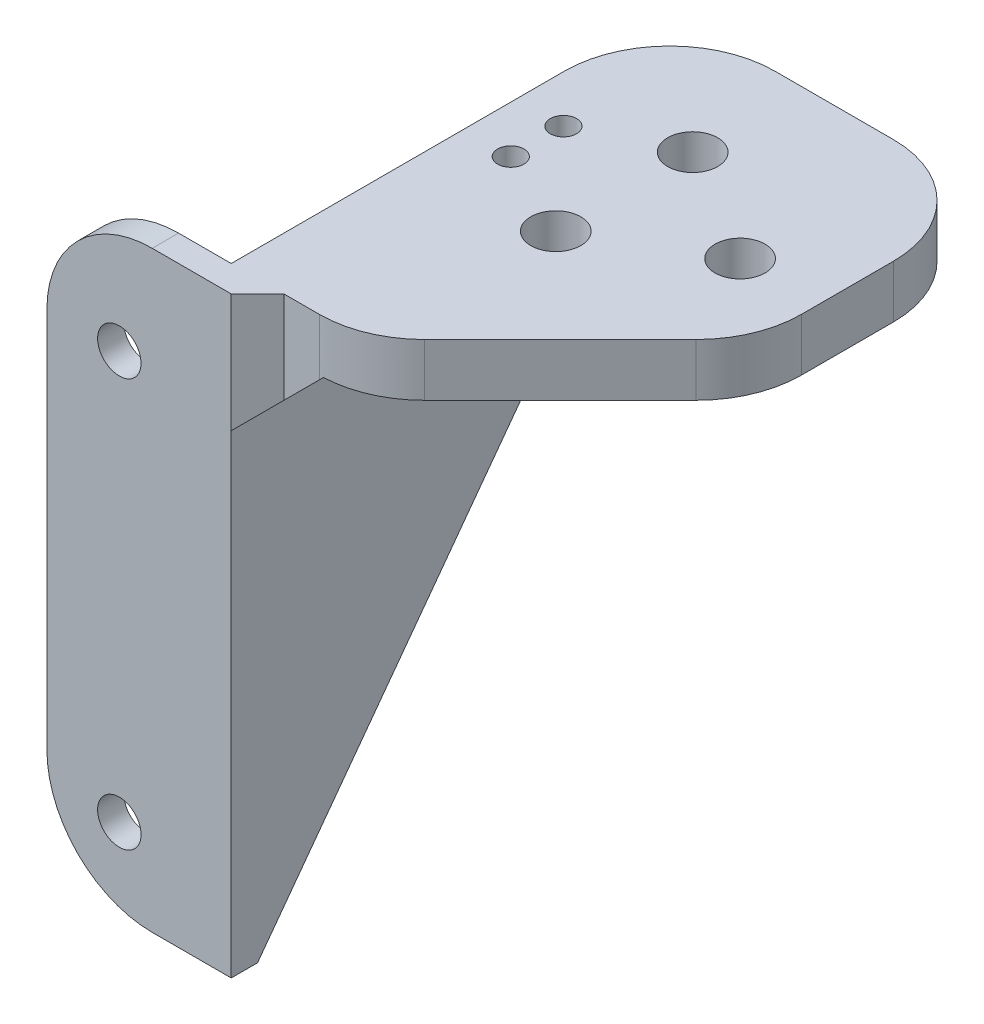
SolidWorks part; units mm, degrees
ref_plane "Front Plane" through (0, 0, 0) normal (0, 0, 1) x (1, 0, 0)
ref_plane "Top Plane" through (0, 0, 0) normal (0, 1, 0) x (1, 0, 0)
ref_plane "Right Plane" through (0, 0, 0) normal (1, 0, 0) x (0, 0, -1)
sketch "Sketch1" plane through (0, 0, 0) normal (0, 0, 1) x (1, 0, 0)
  line L0 (-6.5, 37) -> (-6.5, 6) construction
  line L1 (0, 0) -> (-12, 0)
  line L2 (0, 0) -> (0, 45)
  line L3 (0, 45) -> (-12, 45)
  line L4 (-12, 0) -> (-12, 45)
  circle A0 centre (-6.5, 37) radius 1.65
  circle A1 centre (-6.5, 6) radius 1.65
  dimension "D6" = 3.3
  dimension "D1" = 31
  dimension "D2" = 12
  dimension "D3" = 6.5
  dimension "D4" = 6
  dimension "D5" = 45
extrude "Boss-Extrude1" add sketch "Sketch1" against normal blind 2
sketch "Sketch2" plane through (0, 0, 0) normal (1, 0, 0) x (0, 0, -1)
  line L0 (35.3, 45) -> (2, 0)
  line L1 (0, 45) -> (35.3, 45)
  line L2 (0, 45) -> (0, 0)
  line L3 (0, 0) -> (2, 0)
  line L5 (2, 0) -> (2, 45) construction
  line L6 (2, 0) -> (0, 0) construction
  point P1 (2, -2.3463)
  dimension "D1" = 35.3
extrude "Boss-Extrude2" add sketch "Sketch2" along normal blind 2
sketch "Sketch3" plane through (0, 45, 0) normal (0, 1, 0) x (1, 0, 0)
  line L0 (0, 2) -> (-12, 2) construction
  line L1 (0, 35.3) -> (25, 35.3)
  line L2 (0, 35.3) -> (0, 2)
  line L3 (0, 2) -> (25, 2)
  line L4 (25, 35.3) -> (25, 2)
  point P7 (0, 0)
  dimension "D1" = 25
  dimension "D2" = 33.3
extrude "Boss-Extrude3" add sketch "Sketch3" against normal blind 4
sketch "Sketch4" plane through (0, 45, 0) normal (0, 1, 0) x (1, 0, 0)
  line L1 (6.2, 32.85) -> (24, 32.85) construction
  line L2 (6.2, 32.85) -> (6.2, 10.45) construction
  line L3 (6.2, 10.45) -> (24, 10.45) construction
  line L4 (24, 32.85) -> (24, 10.45) construction
  line L5 (6.2, 21.65) -> (24, 21.65) construction
  line L6 (12.5, 35.3) -> (12.5, 2) construction
  line L7 (25, 35.3) -> (0, 35.3) construction
  line L8 (2, 2) -> (25, 2) construction
  line L11 (25, 2) -> (25, 35.3) construction
  circle A0 centre (10.2, 26.85) radius 1.9
  circle A1 centre (10.2, 16.45) radius 1.9
  circle A2 centre (19, 21.65) radius 1.9
  point P26 (18.1131, 16)
  point P27 (7.2439, 21.2198)
  point P28 (7.6158, 10.3093)
  dimension "D3" = 3.8
  dimension "D1" = 17.8
  dimension "D2" = 22.4
  dimension "D4" = 4
  dimension "D5" = 6
  dimension "D6" = 6
  dimension "D7" = 4
  dimension "D8" = 5
  dimension "D9" = 1
  dimension "D10" = 8.45
extrude "Cut-Extrude1" cut sketch "Sketch4" against normal up to surface (4 mm away) up to face at (9, 41, -23.2133)
sketch "Sketch5" plane through (0, 45, 0) normal (0, 1, 0) x (1, 0, 0)
  line L0 (0, 21.65) -> (25, 21.65) construction
  line L1 (0, 35.3) -> (0, 2) construction
  line L3 (3.5826, 23.65) -> (3.5826, 19.65) construction
  circle A0 centre (3.5826, 23.65) radius 1
  circle A1 centre (3.5826, 19.65) radius 1
  circle A2 centre (19, 21.65) radius 1.9 construction
  circle A3 centre (19, 21.65) radius 1.9
  dimension "D1" = 2
  dimension "D2" = 4
extrude "Cut-Extrude2" cut sketch "Sketch5" against normal through all
sketch "Sketch6" plane through (0, 45, 0) normal (0, 1, 0) x (1, 0, 0)
  line L0 (10, 2) -> (25, 17)
  line L1 (2, 2) -> (25, 2) construction
  line L2 (25, 2) -> (25, 35.3) construction
  line L3 (25, 17) -> (25, 2)
  line L4 (25, 2) -> (10, 2)
  dimension "D1" = 45
  dimension "D2" = 15
extrude "Cut-Extrude3" cut sketch "Sketch6" against normal up to surface (4 mm away) up to face at (3.5826, 41, -18.65)
chamfer "Chamfer1" distance 5 angle 45 1 edges at (2, 41, -17.17)
chamfer "Chamfer2" distance 2 angle 45 1 edges at (2, 40.5, -2)
fillet "Fillet1" radius 8 2 edges at (-12, 0, -1) (-12, 45, -1)
fillet "Fillet2" radius 8 2 edges at (0, 43, -35.3) (25, 43, -35.3)
fillet "Fillet3" radius 8 2 edges at (10, 43, -2) (25, 43, -17)
